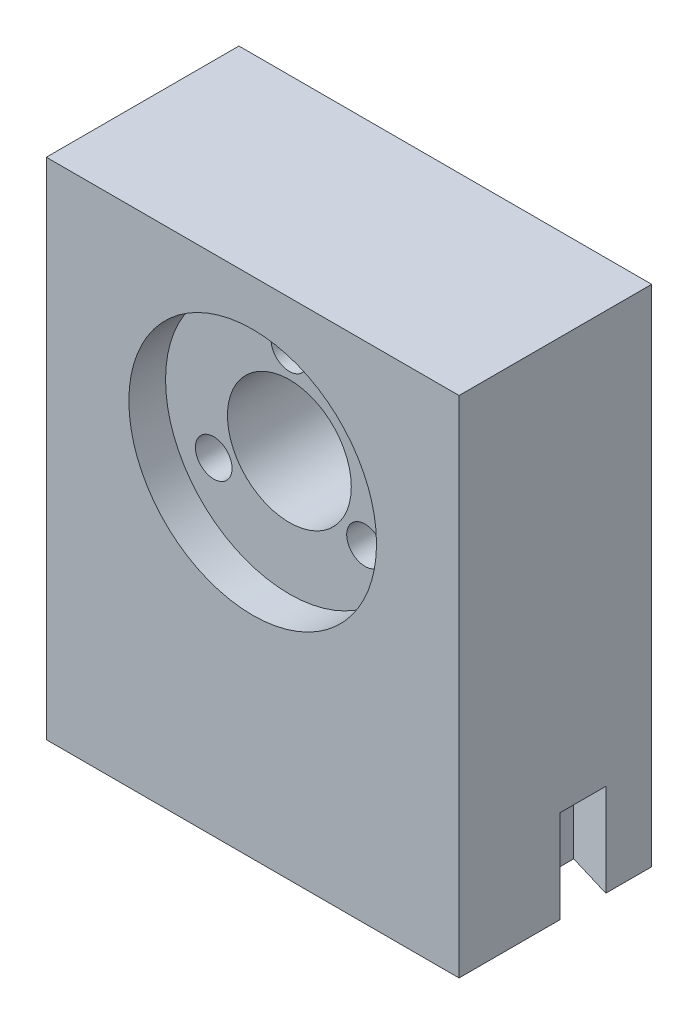
SolidWorks part; units mm, degrees
ref_plane "Front Plane" through (0, 0, 0) normal (0, 0, 1) x (1, 0, 0)
ref_plane "Top Plane" through (0, 0, 0) normal (0, 1, 0) x (1, 0, 0)
ref_plane "Right Plane" through (0, 0, 0) normal (1, 0, 0) x (0, 0, -1)
sketch "Sketch1" plane through (0, 0, 0) normal (0, 0, 1) x (1, 0, 0)
  line L1 (0, 0) -> (45, 0)
  line L2 (0, 0) -> (0, 55)
  line L3 (0, 55) -> (45, 55)
  line L4 (45, 0) -> (45, 55)
  dimension "D1" = 45
  dimension "D2" = 55
extrude "Boss-Extrude1" add sketch "Sketch1" along normal blind 15
sketch "Sketch2" plane through (0, 0, 15) normal (0, 0, 1) x (1, 0, 0)
  line L0 (0, 0) -> (45, 0) construction
  line L1 (22.5, 55) -> (22.5, 0) construction
  line L2 (45, 55) -> (0, 55) construction
  line L3 (14.5, 0) -> (30.5, 0)
  line L4 (14.5, 0) -> (14.5, 2)
  line L5 (14.5, 2) -> (21.5, 2)
  line L6 (30.5, 0) -> (30.5, 2)
  line L7 (23.5, 2) -> (30.5, 2)
  line L9 (21.5, 2) -> (21.5, 10)
  line L10 (21.5, 10) -> (23.5, 10)
  line L11 (23.5, 2) -> (23.5, 10)
  point P14 (22.5, 0)
  dimension "D1" = 16
  dimension "D2" = 2
  dimension "D3" = 2
  dimension "D5" = 8
extrude "Cut-Extrude1" cut sketch "Sketch2" against normal through all
sketch "Sketch3" plane through (0, 0, 0) normal (0, -1, 0) x (1, 0, 0)
  line L0 (45, 10) -> (40, 11.5)
  line L1 (45, 15) -> (45, 0) construction
  line L2 (40, 11.5) -> (40, 3.5)
  line L3 (40, 3.5) -> (45, 5)
  line L4 (45, 10) -> (45, 5)
  point P7 (45, 7.5)
  dimension "D1" = 8
  dimension "D2" = 5
  dimension "D3" = 5
extrude "Cut-Extrude2" cut sketch "Sketch3" against normal blind 10.1
ref_plane "Plane1" through (22.5, 0, 0) normal (1, 0, 0) x (0, 0, -1)
mirror "Mirror1" about plane through (22.5, 0, 0) normal (1, 0, 0) of "Cut-Extrude2"
sketch "Sketch4" plane through (0, 0, 15) normal (0, 0, 1) x (1, 0, 0)
  line L1 (0, 55) -> (45, 55)
  line L2 (0, 55) -> (0, 0)
  line L3 (0, 0) -> (45, 0)
  line L4 (45, 55) -> (45, 0)
extrude "Boss-Extrude2" add sketch "Sketch4" along normal blind 3
sketch "Sketch5" plane through (0, 0, 18) normal (0, 0, 1) x (1, 0, 0)
  line L0 (0, 0) -> (45, 0) construction
  circle A0 centre (22.5, 0) radius 17.5
  dimension "D1" = 35
extrude "Cut-Extrude3" cut sketch "Sketch5" against normal up to surface (3 mm away) up to face at (21.5, 3.5, 15)
sketch "Sketch6" plane through (0, 0, 18) normal (0, 0, 1) x (1, 0, 0)
  line L1 (0, 55) -> (45, 55)
  line L2 (0, 55) -> (0, 0)
  line L3 (0, 0) -> (45, 0)
  line L4 (45, 55) -> (45, 0)
extrude "Boss-Extrude3" add sketch "Sketch6" along normal blind 3
sketch "Sketch7" plane through (0, 0, 21) normal (0, 0, 1) x (1, 0, 0)
  line L0 (0, 36.5) -> (45, 36.5) construction
  line L1 (0, 55) -> (0, 0) construction
  line L2 (45, 0) -> (45, 55) construction
  line L3 (45, 55) -> (0, 55) construction
  circle A0 centre (22.5, 36.5) radius 4.5
  dimension "D2" = 9
  dimension "D1" = 18.5
extrude "Cut-Extrude4" cut sketch "Sketch7" against normal through all
sketch "Sketch8" plane through (0, 0, 21) normal (0, 0, 1) x (1, 0, 0)
  circle A0 centre (22.5, 36.5) radius 9.525 construction
  circle A1 centre (22.5, 46.025) radius 2
  circle A2 centre (30.7489, 31.7375) radius 2
  circle A3 centre (14.2511, 31.7375) radius 2
  point P11 (22.5, 36.5)
  dimension "D1" = 19.05
  dimension "D2" = 4
  dimension "D3" = 3
extrude "Cut-Extrude5" cut sketch "Sketch8" against normal through all
sketch "Sketch9" plane through (0, 0, 21) normal (0, 0, 1) x (1, 0, 0)
  circle A0 centre (22.5, 36.5) radius 13.5
  dimension "D1" = 27
extrude "Cut-Extrude6" cut sketch "Sketch9" against normal blind 4
sketch "Sketch10" plane through (0, 0, 17) normal (0, 0, 1) x (1, 0, 0)
  circle A0 centre (22.5, 36.5) radius 6.75
  dimension "D1" = 13.5
extrude "Cut-Extrude7" cut sketch "Sketch10" against normal blind 10
